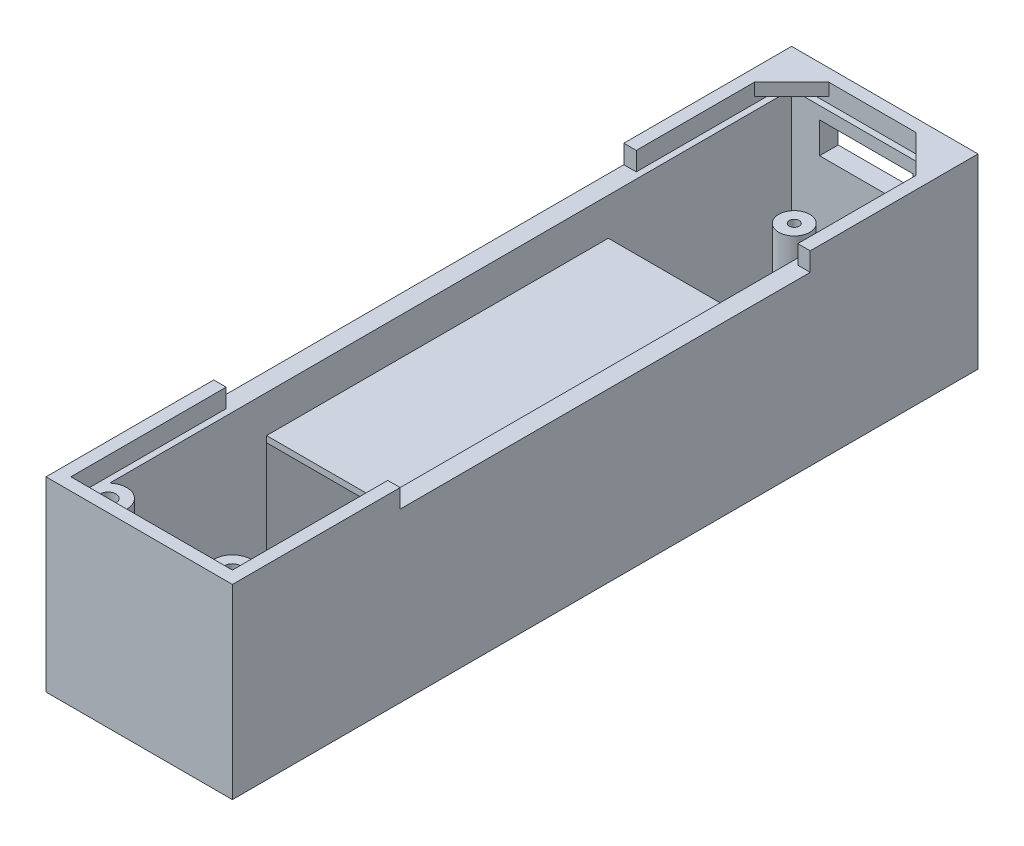
SolidWorks part; units mm, degrees
ref_plane "Front" through (0, 0, 0) normal (0, 0, 1) x (1, 0, 0)
ref_plane "Top" through (0, 0, 0) normal (0, 1, 0) x (1, 0, 0)
ref_plane "Right" through (0, 0, 0) normal (1, 0, 0) x (0, 0, -1)
sketch "Sketch1" plane through (0, 0, 0) normal (0, 1, 0) x (1, 0, 0)
  line L1 (-15, -60) -> (15, -60)
  line L2 (-15, -60) -> (-15, 60)
  line L3 (-15, 60) -> (15, 60)
  line L4 (15, -60) -> (15, 60)
  line L5 (-15, -60) -> (15, 60) construction
  line L6 (-15, 60) -> (15, -60) construction
  point P0 (0, 0)
  dimension "D1" = 120
  dimension "D2" = 30
extrude "Boss-Extrude1" add sketch "Sketch1" along normal blind 30 contours L2 L3 L4 L1
sketch "Sketch3" plane through (0, 30, 0) normal (0, 1, 0) x (1, 0, 0)
  line L1 (-12, -57) -> (12, -57)
  line L2 (-12, -57) -> (-12, 57)
  line L3 (-12, 57) -> (12, 57)
  line L4 (12, -57) -> (12, 57)
  line L5 (-12, -57) -> (12, 57) construction
  line L6 (-12, 57) -> (12, -57) construction
  point P0 (0, 0)
  dimension "D1" = 114
  dimension "D2" = 24
extrude "Cut-Extrude1" cut sketch "Sketch3" against normal blind 27.5
sketch "Sketch4" plane through (0, 30, 0) normal (0, 1, 0) x (1, 0, 0)
  line L1 (-13, -58) -> (13, -58)
  line L2 (-13, -58) -> (-13, 58)
  line L3 (-13, 58) -> (13, 58)
  line L4 (13, -58) -> (13, 58)
  line L5 (-13, -58) -> (13, 58) construction
  line L6 (-13, 58) -> (13, -58) construction
  point P0 (0, 0)
  dimension "D1" = 26
  dimension "D2" = 116
extrude "Cut-Extrude2" cut sketch "Sketch4" against normal blind 3
sketch "Sketch5" plane through (15, 0, 0) normal (1, 0, 0) x (0, 0, -1)
  line L0 (-60, 30) -> (60, 30) construction
  line L1 (-33, 27) -> (33, 27)
  line L2 (-33, 27) -> (-33, 30)
  line L3 (-33, 30) -> (33, 30)
  line L4 (33, 27) -> (33, 30)
  line L5 (-33, 27) -> (33, 30) construction
  line L6 (-33, 30) -> (33, 27) construction
  line L7 (0, 28.5) -> (0, 0) construction
  point P0 (0, 28.5)
  dimension "D1" = 66
  dimension "D2" = 3
extrude "Cut-Extrude3" cut sketch "Sketch5" against normal through all
sketch "Sketch6" plane through (0, 0, 0) normal (0, -1, 0) x (1, 0, 0)
  line L1 (-12.5, -27.5) -> (12.5, -27.5)
  line L2 (-12.5, -27.5) -> (-12.5, 27.5)
  line L3 (-12.5, 27.5) -> (12.5, 27.5)
  line L4 (12.5, -27.5) -> (12.5, 27.5)
  line L5 (-12.5, -27.5) -> (12.5, 27.5) construction
  line L6 (-12.5, 27.5) -> (12.5, -27.5) construction
  point P0 (0, 0)
  dimension "D1" = 25
  dimension "D2" = 55
extrude "Cut-Extrude4" cut sketch "Sketch6" against normal blind 20
sketch "Sketch8" plane through (0, 20, 0) normal (0, -1, 0) x (1, 0, 0)
  line L1 (12, 27.5) -> (-12, 27.5)
  line L2 (12, 27.5) -> (12, -27.5)
  line L3 (12, -27.5) -> (-12, -27.5)
  line L4 (-12, 27.5) -> (-12, -27.5)
  line L5 (12, 27.5) -> (-12, -27.5) construction
  line L6 (12, -27.5) -> (-12, 27.5) construction
  point P0 (0, 0)
extrude "Boss-Extrude2" add sketch "Sketch8" against normal blind 1
sketch "Sketch9" plane through (0, 0, -60) normal (0, 0, -1) x (-1, 0, 0)
  line L0 (0, 0) -> (0, 30) construction
  line L1 (7.5, 25) -> (-7.5, 25)
  line L2 (7.5, 25) -> (7.5, 20)
  line L3 (7.5, 20) -> (-7.5, 20)
  line L4 (-7.5, 25) -> (-7.5, 20)
  line L5 (7.5, 25) -> (-7.5, 20) construction
  line L6 (7.5, 20) -> (-7.5, 25) construction
  line L7 (15, 0) -> (-15, 0) construction
  line L8 (15, 30) -> (-15, 30) construction
  point P0 (0, 22.5)
  dimension "D1" = 5
  dimension "D2" = 15
  dimension "D3" = 5
extrude "Cut-Extrude5" cut sketch "Sketch9" against normal up to surface (3 mm away) up to face at (0, 14.75, -57)
sketch "Sketch10" plane through (0, 2.5, 0) normal (0, 1, 0) x (1, 0, 0)
  line L0 (0, 0) -> (0, 57) construction
  line L1 (12, 57) -> (-12, 57) construction
  line L2 (-12, 42.25) -> (12, 42.25) construction
  line L3 (-12, 57) -> (-12, 27.5) construction
  line L4 (12, 27.5) -> (12, 57) construction
  circle A0 centre (-7.62, 31.455) radius 2.5
  circle A1 centre (-7.62, 53.045) radius 2.5
  circle A2 centre (7.62, 53.045) radius 2.5
  circle A3 centre (7.62, 31.455) radius 2.5
  point P13 (-7.62, 53.045)
  point P16 (7.62, 31.455)
  point P17 (7.62, 53.045)
  dimension "D2" = 5
  dimension "D1" = 21.59
  dimension "D3" = 15.24
extrude "Boss-Extrude3" add sketch "Sketch10" along normal blind 10
sketch "Sketch13" plane through (0, 27, 0) normal (0, 1, 0) x (1, 0, 0)
  line L0 (0, -57) -> (0, -37.9781) construction
  line L1 (-12, -57) -> (12, -57) construction
  line L2 (-12, -27.5) -> (-12, -57) construction
  line L3 (-12, -57) -> (12, -57) construction
  line L4 (-12, 57) -> (-12, -57) construction
  line L5 (-12, -52.7639) -> (-12, -57)
  line L6 (-12, -57) -> (-7.7639, -57)
  line L7 (12, -57) -> (7.7639, -57)
  line L8 (12, -52.7639) -> (12, -57)
  arc A0 (-12, -52.7639) -> (-7.7639, -57) centre (-10, -55) cw
  arc A1 (12, -52.7639) -> (7.7639, -57) centre (10, -55) ccw
  dimension "D1" = 3
  dimension "D2" = 2
  dimension "D3" = 2
extrude "Boss-Extrude4" add sketch "Sketch13" against normal up to surface (24.5 mm away) up to face at (0, 2.5, 42.25)
hole_wizard "M2x0.4 Tapped Hole1" positions "Sketch11" profile "Sketch12" tap size "M2x0.4" standard "ANSI Metric"
sketch "Sketch11" plane through (0, 12.5, 0) normal (0, 1, 0) x (1, 0, 0)
  point P0 (-7.62, 31.455)
  point P3 (-7.62, 53.045)
  point P6 (7.62, 53.045)
  point P9 (7.62, 31.455)
sketch "Sketch12" plane through (-7.62, 12.5, -31.455) normal (1, 0, 0) x (0, 0, 1)
  line L0 (0, 0) -> (0, 5.6807)
  line L1 (0, 5.6807) -> (0.8, 5.2)
  line L2 (0.8, 5.2) -> (0.8, 0)
  line L5 (0.8, 0) -> (0, 0)
  line L10 (0, 5.6807) -> (-0.8, 5.2) construction
  line L11 (0, -6.35) -> (0, 107.95) construction
  dimension "Tap Drill Dia." = 1.6
  dimension "Tap Drill Depth" = 5.2
  dimension "Drill Angle" = 118
cosmetic thread "Hole Thread1" parameters "D1"=4, "D2"=2
cosmetic thread "Hole Thread2" parameters "D1"=4, "D2"=2
cosmetic thread "Hole Thread3" parameters "D1"=4, "D2"=2
cosmetic thread "Hole Thread4" parameters "D1"=4, "D2"=2
hole_wizard "Tap Drill for M3x0.5 Tap2" positions "Sketch18" profile "Sketch19" hole size "M3x0.5" standard "ANSI Metric" end condition through all
sketch "Sketch18" plane through (0, 27, 0) normal (0, 1, 0) x (1, 0, 0)
  point P0 (-10, -55)
  point P3 (10, -55)
sketch "Sketch19" plane through (-10, 27, 55) normal (1, 0, 0) x (0, 0, 1)
  line L0 (0, 0) -> (0, 27)
  line L1 (0, 27) -> (1.25, 27)
  line L2 (1.25, 27) -> (1.25, 0)
  line L5 (1.25, 0) -> (0, 0)
  line L11 (0, -6.35) -> (0, 107.95) construction
  dimension "Thru Hole Dia." = 2.5
  dimension "Thru Hole Depth" = 27
sketch "Sketch21" plane through (0, 30, 0) normal (0, 1, 0) x (1, 0, 0)
  line L0 (-13, 52) -> (-7, 58)
  line L1 (-13, 58) -> (-13, 33) construction
  line L2 (13, 58) -> (-13, 58) construction
  line L3 (-7, 58) -> (-13, 58)
  line L4 (-13, 58) -> (-13, 52)
  line L5 (0, 58) -> (0, 52.1711) construction
  line L6 (13, 58) -> (-13, 58) construction
  line L7 (13, 58) -> (13, 52)
  line L8 (7, 58) -> (13, 58)
  line L9 (13, 52) -> (7, 58)
  dimension "D1" = 6
  dimension "D2" = 6
extrude "Boss-Extrude7" add sketch "Sketch21" against normal blind 2
